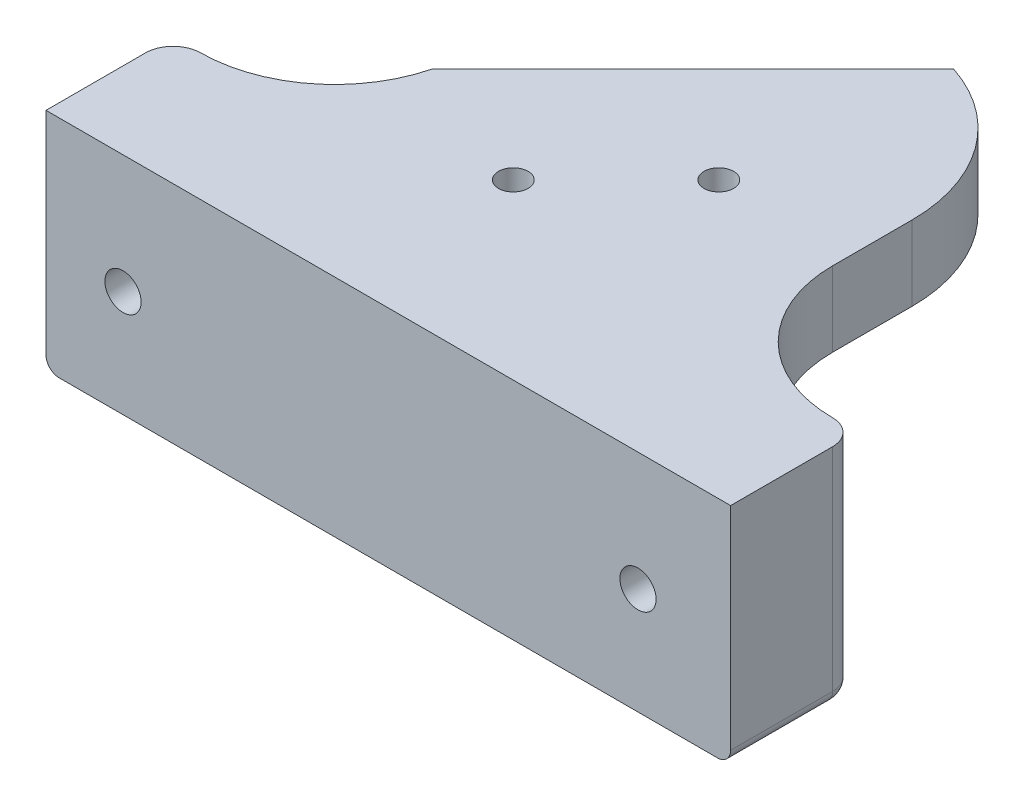
SolidWorks part; units mm, degrees
ref_plane "Front Plane" through (0, 0, 0) normal (0, 0, 1) x (1, 0, 0)
ref_plane "Top Plane" through (0, 0, 0) normal (0, 1, 0) x (1, 0, 0)
ref_plane "Right Plane" through (0, 0, 0) normal (1, 0, 0) x (0, 0, -1)
sketch "Sketch1" plane through (0, 0, 0) normal (0, 0, 1) x (1, 0, 0)
  line L5 (-69.4768, -14.6899) -> (34.4916, -14.6899)
  line L6 (-69.4768, -14.6899) -> (-69.4768, 19.4962)
  line L7 (-69.4768, 19.4962) -> (34.4916, 19.4962)
  line L8 (34.4916, -14.6899) -> (34.4916, 19.4962)
extrude "Boss-Extrude1" add sketch "Sketch1" along normal blind 19.3
sketch "Sketch2" plane through (0, 0, 0) normal (0, 0, -1) x (-1, 0, 0)
  line L0 (69.4768, 19.4962) -> (69.4768, -14.6899) construction
  line L1 (69.4768, 8.1286) -> (-34.4916, 8.1286)
  line L2 (69.4768, 8.1286) -> (69.4768, 19.4962)
  line L3 (69.4768, 19.4962) -> (-34.4916, 19.4962)
  line L4 (-34.4916, 8.1286) -> (-34.4916, 19.4962)
  line L5 (-34.4916, 19.4962) -> (69.4768, 19.4962) construction
  line L6 (-34.4916, -14.6899) -> (-34.4916, 19.4962) construction
extrude "Boss-Extrude2" add sketch "Sketch2" along normal blind 60
sketch "Sketch3" plane through (0, 8.1286, 0) normal (0, -1, 0) x (1, 0, 0)
  line L0 (-45.5992, 0) -> (-45.5992, -15.4)
  line L1 (-69.4768, 0) -> (34.4916, 0) construction
  line L2 (-45.5992, 0) -> (-45.5992, -15.4) construction
  line L3 (-45.5992, -15.4) -> (-5.9598, -55.0394)
  line L7 (34.4916, 19.3) -> (34.4916, 0) construction
  line L8 (34.4916, -60) -> (34.4916, 0) construction
  line L9 (34.4916, 0) -> (34.4916, -60)
  line L10 (34.4916, -60) -> (-69.4768, -60) construction
  line L11 (34.4916, -60) -> (-69.4768, -60)
  line L12 (-69.4768, -60) -> (-69.4768, 0)
  line L13 (-69.4768, 0) -> (-45.5992, 0)
  line L20 (34.4916, 0) -> (10.7044, 0)
  line L21 (10.7044, 0) -> (10.7044, -55.0394)
  line L22 (10.7044, -55.0394) -> (-5.9598, -55.0394)
  line L23 (-45.5992, -15.4) -> (-5.5992, -55.4) construction
  line L24 (-11.6167, -60.6962) -> (-5.9598, -55.0394) construction
extrude "Cut-Extrude1" cut sketch "Sketch3" against normal through all
hole_wizard "M4 Clearance Hole1" positions "3DSketch2" profile "Sketch4" hole size "M4" standard "ISO" end condition through all
sketch3d "3DSketch2"
  point P0 (-9.2371, 8.1286, -22.6408)
  point P2 (-24.8421, 8.1286, -7.0358)
sketch "Sketch4" plane through (-9.2371, 8.1286, -22.6408) normal (1, 0, 0) x (0, 0, -1)
  line L0 (0, 0) -> (0, 11.3676)
  line L1 (0, 11.3676) -> (2.25, 11.3676)
  line L2 (2.25, 11.3676) -> (2.25, 0)
  line L5 (2.25, 0) -> (0, 0)
  line L11 (0, -6.35) -> (0, 107.95) construction
  dimension "Thru Hole Dia." = 4.5
  dimension "Thru Hole Depth" = 11.3676
hole_wizard "M5 Clearance Hole1" positions "3DSketch3" profile "Sketch5" hole size "M5" standard "ISO" end condition through all
sketch3d "3DSketch3"
  point P0 (-57.7823, 1.4985, 0)
  point P2 (20.4265, 1.4985, 0)
sketch "Sketch5" plane through (-57.7823, 1.4985, 0) normal (1, 0, 0) x (0, 1, 0)
  line L0 (0, 0) -> (0, 19.3)
  line L1 (0, 19.3) -> (2.75, 19.3)
  line L2 (2.75, 19.3) -> (2.75, 0)
  line L5 (2.75, 0) -> (0, 0)
  line L11 (0, -6.35) -> (0, 107.95) construction
  dimension "Thru Hole Dia." = 5.5
  dimension "Thru Hole Depth" = 19.3
fillet "Fillet1" radius 20 1 edges at (10.7044, 13.8124, 0)
fillet "Fillet2" radius 20.5 1 edges at (-45.5992, 13.8124, 0)
fillet "Fillet4" radius 4.2 1 edges at (-69.4768, 2.4032, 0)
fillet "Fillet8" radius 3.8 1 edges at (34.4916, 2.4032, 0)
fillet "Fillet9" radius 24.2 1 edges at (10.7044, 13.8124, -55.0394)
fillet "Fillet10" radius 2 5 edges at (-69.4768, -14.6899, 11.75) (-68.2466, -14.6899, 1.2302) (34.4916, -14.6899, 11.55) (33.3786, -14.6899, 1.113) (-17.2926, -14.6899, 0)
